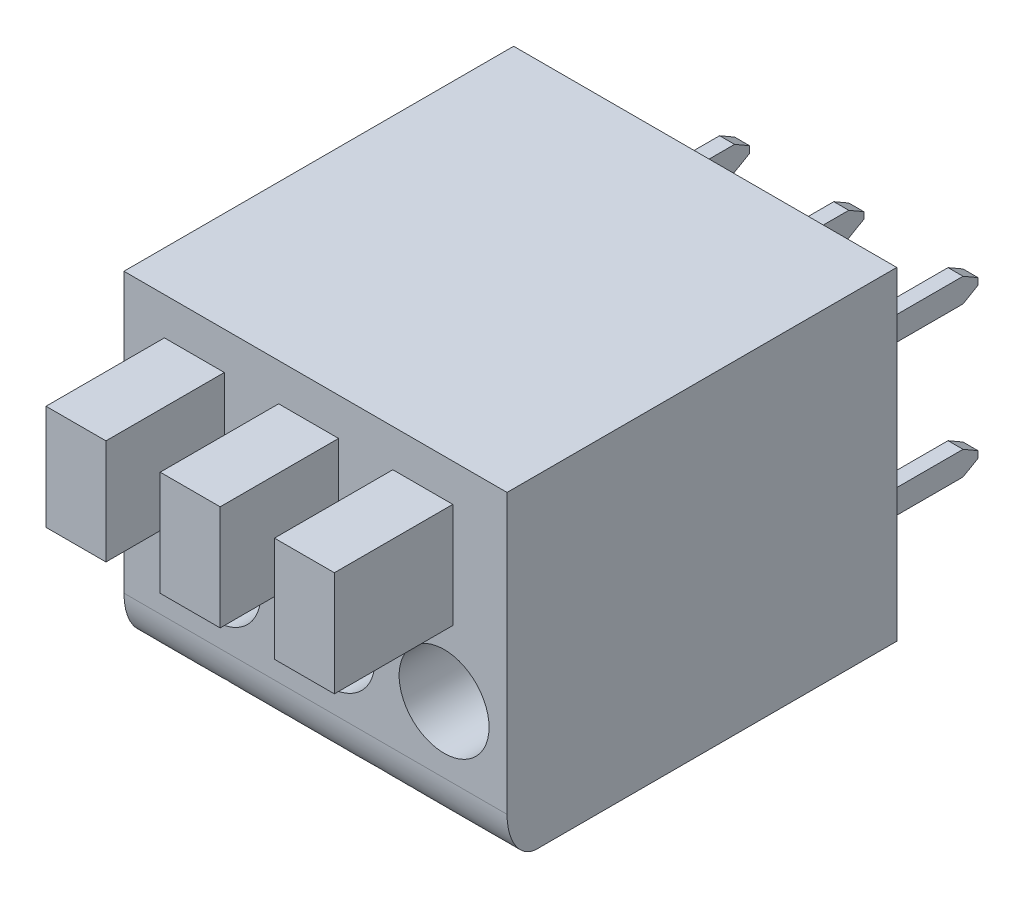
SolidWorks part; units mm, degrees
ref_plane "Спереди" through (0, 0, 0) normal (0, 0, 1) x (1, 0, 0)
ref_plane "Сверху" through (0, 0, 0) normal (0, 1, 0) x (1, 0, 0)
ref_plane "Справа" through (0, 0, 0) normal (1, 0, 0) x (0, 0, -1)
sketch "Эскиз1" plane through (0, 0, 0) normal (0, 0, 1) x (1, 0, 0)
  line L1 (-6.39, -5.4) -> (6.39, -5.4)
  line L2 (-6.39, -5.4) -> (-6.39, 5.4)
  line L3 (-6.39, 5.4) -> (6.39, 5.4)
  line L4 (6.39, -5.4) -> (6.39, 5.4)
  line L5 (-6.39, -5.4) -> (6.39, 5.4) construction
  line L6 (-6.39, 5.4) -> (6.39, -5.4) construction
  point P0 (0, 0)
  dimension "D1" = 12.78
  dimension "D2" = 10.8
extrude "Бобышка-Вытянуть1" add sketch "Эскиз1" along normal blind 13
fillet "Скругление1" radius 1 1 edges at (0, -5.4, 13) second distance 1.5 first distance on face at (0, -5.4, 6.5)
sketch "Эскиз2" plane through (0, 0, 13) normal (0, 0, 1) x (1, 0, 0)
  line L0 (6.39, -3.9) -> (6.39, 5.4) construction
  line L1 (2.58, 0.65) -> (4.58, 0.65)
  line L2 (2.58, 0.65) -> (2.58, 4.15)
  line L3 (2.58, 4.15) -> (4.58, 4.15)
  line L4 (4.58, 0.65) -> (4.58, 4.15)
  line L5 (2.58, 0.65) -> (4.58, 4.15) construction
  line L6 (2.58, 4.15) -> (4.58, 0.65) construction
  line L7 (6.39, 5.4) -> (-6.39, 5.4) construction
  point P0 (3.58, 2.4)
  dimension "D1" = 3.5
  dimension "D2" = 2
  dimension "D3" = 3.81
  dimension "D4" = 4.75
extrude "Бобышка-Вытянуть2" add sketch "Эскиз2" along normal blind 3.95
sketch "Эскиз3" plane through (0, 0, 13) normal (0, 0, 1) x (1, 0, 0)
  line L0 (6.39, -3.9) -> (6.39, 5.4) construction
  circle A0 centre (4.29, -1.686) radius 1.5
  dimension "D1" = 3
  dimension "D2" = 2.1
extrude "Вырез-Вытянуть1" cut sketch "Эскиз3" against normal blind 3.95
sketch "Эскиз4" plane through (0, 0, 0) normal (0, 0, -1) x (-1, 0, 0)
  line L0 (-6.39, 5.4) -> (6.39, 5.4) construction
  line L1 (-5.6, 2.45) -> (-5.1, 2.45)
  line L2 (-5.6, 2.45) -> (-5.6, 3.25)
  line L3 (-5.6, 3.25) -> (-5.1, 3.25)
  line L4 (-5.1, 2.45) -> (-5.1, 3.25)
  line L5 (-5.6, 2.45) -> (-5.1, 3.25) construction
  line L6 (-5.6, 3.25) -> (-5.1, 2.45) construction
  line L7 (-5.1, -1.75) -> (-5.6, -1.75)
  line L8 (-5.1, -1.75) -> (-5.1, -2.55)
  line L9 (-5.1, -2.55) -> (-5.6, -2.55)
  line L10 (-5.6, -1.75) -> (-5.6, -2.55)
  line L11 (-5.1, -1.75) -> (-5.6, -2.55) construction
  line L12 (-5.1, -2.55) -> (-5.6, -1.75) construction
  line L14 (-6.39, -5.4) -> (-6.39, 5.4) construction
  point P0 (-5.35, 2.85)
  point P5 (-5.35, -2.15)
  dimension "D1" = 0.5
  dimension "D2" = 0.8
  dimension "D3" = 5
  dimension "D4" = 2.55
  dimension "D5" = 1.04
extrude "Бобышка-Вытянуть3" add sketch "Эскиз4" along normal blind 3.5
chamfer "Фаска1" distance 0.5 angle 30 4 edges at (5.35, -2.55, -3.5) (5.35, -1.75, -3.5) (5.35, 2.45, -3.5) (5.35, 3.25, -3.5) first distance on face at (5.35, -2.55, -1.75) first distance on face at (5.35, -1.75, -1.75) first distance on face at (5.35, 2.45, -1.75) first distance on face at (5.35, 3.25, -1.75)
pattern_linear "Линейный массив2" count 3 spacing 3.81 along (-1, 0, 0) of "Бобышка-Вытянуть2", "Вырез-Вытянуть1", "Бобышка-Вытянуть3", "Фаска1"
